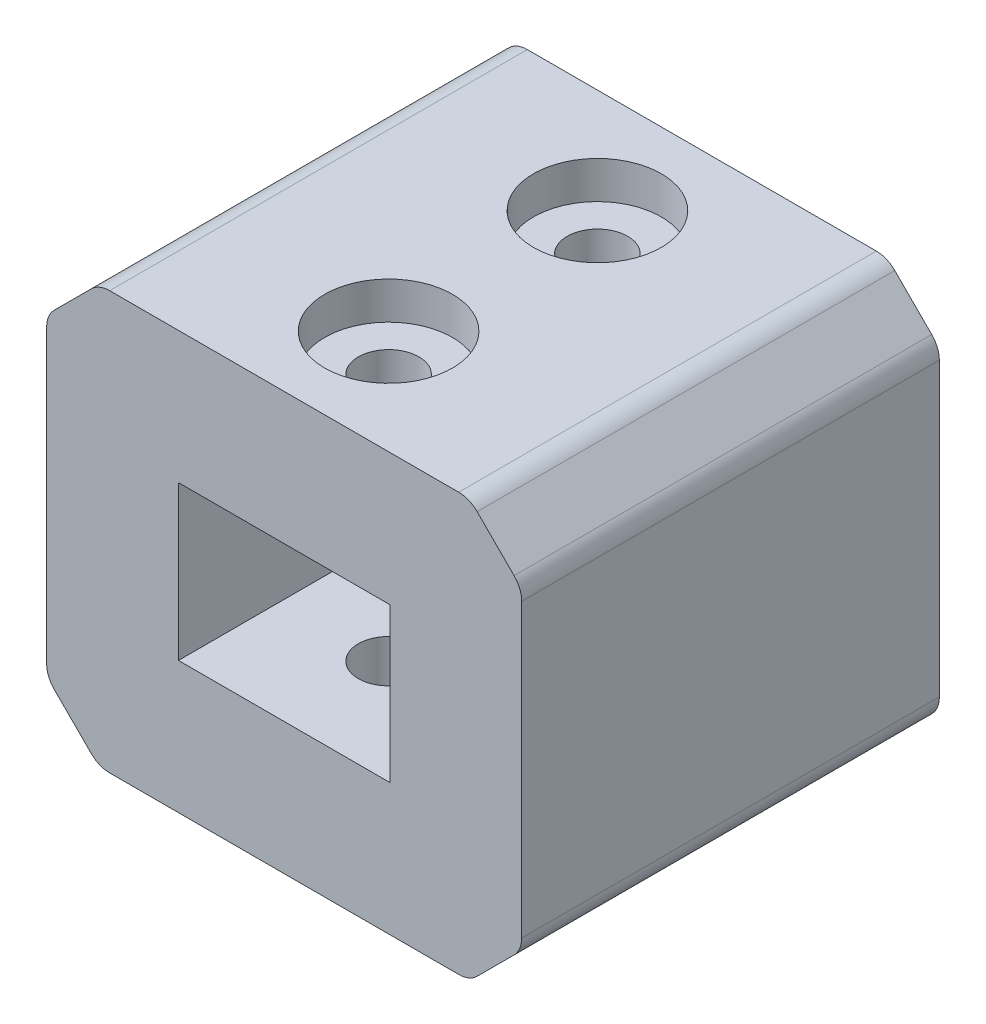
SolidWorks part; units mm, degrees
ref_plane "Front Plane" through (0, 0, 0) normal (0, 0, 1) x (1, 0, 0)
ref_plane "Top Plane" through (0, 0, 0) normal (0, 1, 0) x (1, 0, 0)
ref_plane "Right Plane" through (0, 0, 0) normal (1, 0, 0) x (0, 0, -1)
sketch "Sketch1" plane through (0, 0, 0) normal (0, 0, 1) x (1, 0, 0)
  line L1 (-22.75, 20) -> (22.75, 20)
  line L2 (-22.75, 20) -> (-22.75, -20)
  line L3 (-22.75, -20) -> (22.75, -20)
  line L4 (22.75, 20) -> (22.75, -20)
  line L5 (-22.75, 20) -> (22.75, -20) construction
  line L6 (-22.75, -20) -> (22.75, 20) construction
  line L7 (-10.125, 7.375) -> (10.125, 7.375)
  line L8 (-10.125, 7.375) -> (-10.125, -7.375)
  line L9 (-10.125, -7.375) -> (10.125, -7.375)
  line L10 (10.125, 7.375) -> (10.125, -7.375)
  line L11 (-10.125, 7.375) -> (10.125, -7.375) construction
  line L12 (-10.125, -7.375) -> (10.125, 7.375) construction
  point P0 (0, 0)
  point P6 (0, 0)
  dimension "D1" = 45.5
  dimension "D2" = 40
  dimension "D3" = 14.75
  dimension "D4" = 20.25
extrude "Boss-Extrude1" add sketch "Sketch1" along normal blind 40
chamfer "Chamfer1" distance 5 angle 45 4 edges at (-22.75, 20, 20) (22.75, 20, 20) (22.75, -20, 20) (-22.75, -20, 20)
fillet "Fillet1" radius 2.5 8 edges at (17.75, 20, 20) (22.75, 15, 20) (22.75, -15, 20) (17.75, -20, 20) (-17.75, -20, 20) (-22.75, -15, 20) (-22.75, 15, 20) (-17.75, 20, 20)
hole_wizard "CBORE for M5 Hex Head Bolt1" positions "Sketch2" profile "Sketch3" counterbore size "M5" standard "ANSI Metric" end condition through all
sketch "Sketch2" plane through (0, 20, 0) normal (0, 1, 0) x (1, 0, 0)
  line L0 (0, -22) -> (0, 22) construction
  line L1 (-22, 0) -> (22, 0) construction
  point P0 (0, -10)
  dimension "D1" = 10
sketch "Sketch3" plane through (0, 20, 10) normal (1, 0, 0) x (0, 0, 1)
  line L0 (0, 0) -> (0, 40)
  line L1 (0, 40) -> (2.9, 40)
  line L3 (2.9, 40) -> (2.9, 3.58)
  line L4 (2.9, 3.58) -> (6.12, 3.58)
  line L5 (6.12, 3.58) -> (6.12, 0)
  line L7 (6.12, 0) -> (0, 0)
  line L11 (0, -6.35) -> (0, 107.95) construction
  dimension "Thru Hole Dia." = 5.8
  dimension "Thru Hole Depth" = 40
  dimension "C'Bore Dia." = 12.24
  dimension "C'Bore Depth" = 3.58
ref_plane "Plane1" through (0, 0, 20) normal (0, 0, -1) x (-1, 0, 0)
mirror "Mirror1" about plane through (0, 0, 20) normal (0, 0, -1) of "CBORE for M5 Hex Head Bolt1"
